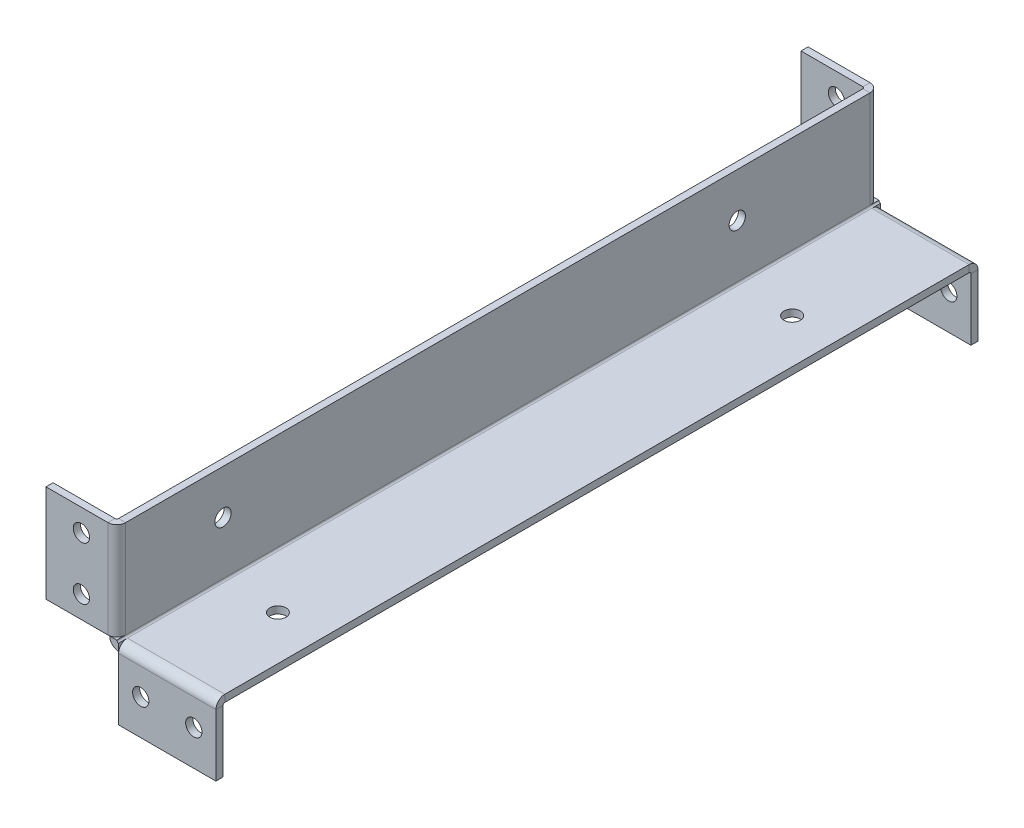
SolidWorks part; units mm, degrees
note: The reader was unsure of these and kept them because the rebuilt part matched: flange length of "Edge-Flange1", "Edge-Flange2".
ref_plane "Front Plane" through (0, 0, 0) normal (0, 0, 1) x (1, 0, 0)
ref_plane "Top Plane" through (0, 0, 0) normal (0, 1, 0) x (1, 0, 0)
ref_plane "Right Plane" through (0, 0, 0) normal (1, 0, 0) x (0, 0, -1)
sketch "Sketch1" plane through (0, 0, 0) normal (0, 1, 0) x (1, 0, 0)
  line L1 (30, 215.25) -> (-30, 215.25)
  line L2 (30, 215.25) -> (30, -215.25)
  line L3 (30, -215.25) -> (-30, -215.25)
  line L4 (-30, 215.25) -> (-30, -215.25)
  line L5 (30, 215.25) -> (-30, -215.25) construction
  line L6 (30, -215.25) -> (-30, 215.25) construction
  point P0 (0, 0)
  dimension "D1" = 60
  dimension "D2" = 430.5
sheet metal parameters "Sheet-Metal1" thickness 4 parameters "D1"=1
base flange "Base-Flange1" sketch "Sketch1" thickness 4 reverse thickness direction yes parameters "D1"=1
edge flange "Edge-Flange1" sketch "Sketch5" flange angle 90 flange length 60 flange position material inside bend radius 1 thickness 4 parameters "D6"=10
sketch "Sketch5" plane through (-30, 4, 0) normal (-1, 0, 0) x (0, 0, 1)
  line L2 (-215.25, 0) -> (-215.25, 56)
  line L3 (-215.25, 56) -> (215.25, 56)
  line L4 (215.25, 56) -> (215.25, 0)
  line L5 (-215.25, 0) -> (215.25, 0) construction
  line L6 (-215.25, 0) -> (215.25, 0)
bend "EdgeBend1" bend radius 1 bend angle 90 parameters "D5"=1
edge flange "Edge-Flange2" sketch "Sketch14" flange profiles "Sketch14", "Sketch15", "Sketch16", "Sketch17" flange angle 90 flange length 40 flange position material inside bend radius 1 thickness 4 relief none parameters "D6"=10, "D8"=0.5
sketch "Sketch14" plane through (-30, 0, 215.25) normal (0, 0, -1) x (0, -1, 0)
  line L1 (-5, 0) -> (-60, 0) construction
  line L2 (-60, 0) -> (-60, 36)
  line L3 (-60, 36) -> (-5, 36)
  line L4 (-5, 36) -> (-5, 0)
  line L5 (-5, 0) -> (-60, 0)
sketch "Sketch15" plane through (0, 0, 215.25) normal (0, 0, -1) x (1, 0, 0)
  line L0 (30, 0) -> (-25, 0) construction
  line L1 (30, 0) -> (-25, 0)
  line L2 (30, 0) -> (30, 36)
  line L3 (30, 36) -> (-25, 36)
  line L4 (-25, 36) -> (-25, 0)
sketch "Sketch16" plane through (-30, 0, -215.25) normal (0, 0, 1) x (0, 1, 0)
  line L0 (60, 0) -> (5, 0) construction
  line L1 (60, 0) -> (5, 0)
  line L2 (60, 0) -> (60, 36)
  line L3 (60, 36) -> (5, 36)
  line L4 (5, 36) -> (5, 0)
sketch "Sketch17" plane through (0, 0, -215.25) normal (0, 0, 1) x (-1, 0, 0)
  line L0 (25, 0) -> (-30, 0) construction
  line L1 (25, 0) -> (-30, 0)
  line L2 (25, 0) -> (25, 36)
  line L3 (25, 36) -> (-30, 36)
  line L4 (-30, 36) -> (-30, 0)
bend "EdgeBend2" bend radius 1 bend angle 90 parameters "D5"=2
bend "EdgeBend3" bend radius 1 bend angle 90 parameters "D5"=3
bend "EdgeBend4" bend radius 1 bend angle 90 parameters "D5"=4
bend "EdgeBend5" bend radius 1 bend angle 90 parameters "D5"=5
sketch "Sketch18" plane through (0, 0, 215.25) normal (0, 0, 1) x (1, 0, 0)
  line L0 (-25, 4) -> (30, 4) construction
  line L1 (-26, 60) -> (-26, 5) construction
  line L2 (-66, 60) -> (-31, 60) construction
  line L3 (30, -1) -> (30, -36) construction
  circle A0 centre (-46, 47.5) radius 4.6
  circle A1 centre (-46, 17.5) radius 4.6
  circle A2 centre (-12.5, -16) radius 4.6
  circle A3 centre (17.5, -16) radius 4.6
  dimension "D7" = 9.2
  dimension "D1" = 30
  dimension "D2" = 30
  dimension "D3" = 20
  dimension "D4" = 20
  dimension "D5" = 12.5
  dimension "D6" = 12.5
extrude "Extrude1" cut sketch "Sketch18" against normal through all normal cut yes
sketch "Sketch19" plane through (-26, 0, 0) normal (1, 0, 0) x (0, 0, -1)
  line L0 (-210.25, 60) -> (210.25, 60) construction
  line L1 (-215.25, 5) -> (-215.25, 60) construction
  line L2 (215.25, 5) -> (215.25, 60) construction
  circle A0 centre (-155.25, 35) radius 4.6
  circle A1 centre (135.25, 35) radius 4.6
  dimension "D4" = 9.2
  dimension "D1" = 25
  dimension "D2" = 60
  dimension "D3" = 80
extrude "Extrude2" cut sketch "Sketch19" against normal blind 4 normal cut yes
sketch "Sketch20" plane through (0, 4, 0) normal (0, 1, 0) x (1, 0, 0)
  line L0 (30, -210.25) -> (30, 210.25) construction
  line L1 (-25, -215.25) -> (30, -215.25) construction
  line L2 (30, 215.25) -> (-25, 215.25) construction
  circle A0 centre (5, 135.25) radius 4.6
  circle A1 centre (5, -155.25) radius 4.6
  dimension "D2" = 9.2
  dimension "D1" = 25
  dimension "D3" = 60
  dimension "D4" = 80
extrude "Extrude3" cut sketch "Sketch20" against normal blind 4 normal cut yes
flat pattern "Flat-Pattern1" [suppressed]
sketch "Bend-Lines1" plane through (0, 4, 0) normal (0, 1, 0) x (-1, 0, 0)
  line L0 (25, -166.9012) -> (-30, -166.9012) construction
  line L1 (82.8023, -166.9012) -> (27.8023, -166.9012) construction
  line L2 (-30, 166.9012) -> (25, 166.9012) construction
  line L3 (27.8023, 166.9012) -> (82.8023, 166.9012) construction
  line L4 (26.4012, -170.5) -> (26.4012, 170.5) construction
  line L5 (25, -166.9012) -> (-30, -166.9012) construction
  line L6 (82.8023, -166.9012) -> (27.8023, -166.9012) construction
  line L7 (-30, 166.9012) -> (25, 166.9012) construction
  line L8 (27.8023, 166.9012) -> (82.8023, 166.9012) construction
  line L9 (26.4012, -170.5) -> (26.4012, 170.5) construction
sketch3d "Bounding-Box1" [suppressed]
  line L0 (52.8023, 32.8023, 0) -> (52.8023, -373.8023, 0) construction
  line L1 (-60, 32.8023, 0) -> (-60, -373.8023, 0) construction
  line L2 (52.8023, 32.8023, 0) -> (-60, 32.8023, 0) construction
  line L3 (52.8023, -373.8023, 0) -> (-60, -373.8023, 0) construction
bend of the flat pattern "Flatten-<EdgeBend1>1"
bend of the flat pattern "Flatten-<EdgeBend2>1"
bend of the flat pattern "Flatten-<EdgeBend3>1"
bend of the flat pattern "Flatten-<EdgeBend4>1"
bend of the flat pattern "Flatten-<EdgeBend5>1"
